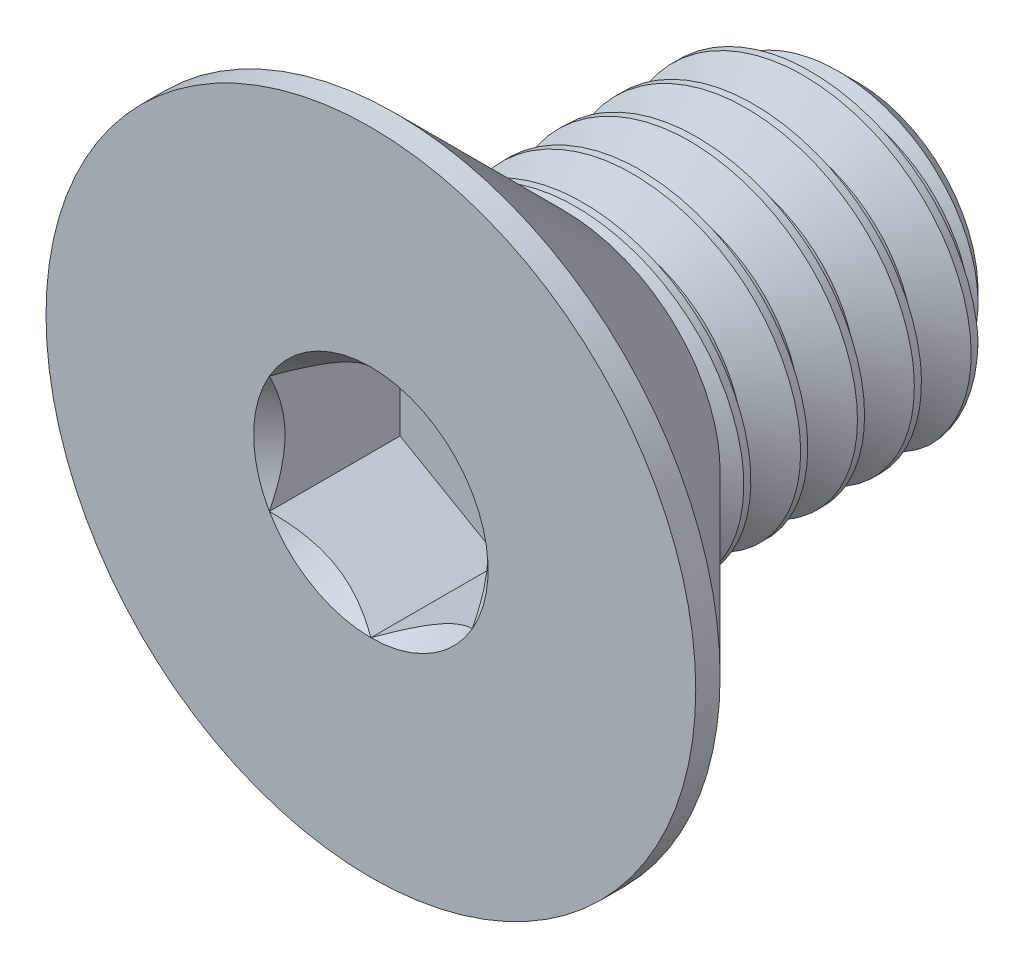
SolidWorks part; units mm, degrees
material "Stainless Steel (ferritic)"
ref_plane "Front" through (0, 0, 0) normal (0, 0, 1) x (1, 0, 0)
ref_plane "Top" through (0, 0, 0) normal (0, 1, 0) x (1, 0, 0)
ref_plane "Right" through (0, 0, 0) normal (1, 0, 0) x (0, 0, -1)
sketch "Sketch1" plane through (0, 0, 0) normal (1, 0, 0) x (0, 0, -1)
  line L0 (0, 4) -> (0.3, 4) construction
  line L1 (0.3, 4) -> (2.3, 2) construction
  line L2 (0, 2) -> (6, 2)
  line L3 (6, 2) -> (6, 0)
  line L4 (6, 0) -> (0, 0)
  line L5 (0, 0) -> (0, 4) construction
  line L6 (0, 4) -> (0, -4) construction
  line L7 (6, 2) -> (6, -2) construction
  line L8 (0, -4) -> (0.3, -4) construction
  line L9 (0.3, -4) -> (2.3, -2) construction
  line L11 (0, 2) -> (0, 0)
  line L12 (2.3, 2) -> (2.3, 0) construction
revolve "Revolve1" add sketch "Sketch1" angle 360 mid plane about L4
sketch "Sketch3" plane through (0, 0, -6) normal (0, 0, -1) x (-1, 0, 0)
  circle A0 centre (0, 0) radius 2
curve "Helix/Spiral1" pitch 0.7 height 6 radius 2 centre (0, 0, -6) axis (0, 0, 1) start towards (0, 1, 0)
sketch "Sketch2" plane through (0, 0, 0) normal (1, 0, 0) x (0, 0, -1)
  line L0 (6, 2) -> (6.6125, 2)
  line L1 (6.6125, 2) -> (6.35, 1.5453)
  line L2 (6.35, 1.5453) -> (6.2625, 1.5453)
  line L3 (6.2625, 1.5453) -> (6, 2)
  line L4 (6.1312, 1.7727) -> (6.4813, 1.7727) construction
  dimension "D1" = 60
  dimension "D2" = 0.0875
  dimension "D3" = 0.35
chamfer "Chamfer1" distance 0.525 angle 45 1 edges at (0, 2, -6)
sweep "Cut-Sweep1" cut profiles "Sketch2" path "Helix/Spiral1" align with end faces yes
sketch "Sketch7" plane through (0, 0, 0) normal (1, 0, 0) x (0, 0, -1)
  line L0 (0, 4) -> (0.3, 4) construction
  line L1 (0.3, 4) -> (2.3, 2) construction
  line L2 (0, 4) -> (0.3, 4)
  line L3 (0.3, 4) -> (2.3, 2)
  line L4 (2.3, 2) -> (2.3, 0) construction
  line L5 (2.3, 2) -> (2.3, 0)
  line L7 (0, 0) -> (0, 4) construction
  line L8 (0, 0) -> (0, 4)
  line L9 (0, 0) -> (2.3, 0)
  line L10 (4.4, 0) -> (-4.4, 0) construction
revolve "Revolve2" add sketch "Sketch7" angle 360 mid plane about L9
ref_plane "Plane1" through (0, 0, -2.3) normal (0, 0, 1) x (1, 0, 0)
sketch "Sketch8" plane through (0, 0, -2.3) normal (0, 0, 1) x (1, 0, 0)
  circle A0 centre (0, 0) radius 2
extrude "Boss-Extrude1" add sketch "Sketch8" against normal through all draft 45
sketch "Sketch5" plane through (0, 0, 0) normal (0, 0, 1) x (1, 0, 0)
  line L1 (1.25, -0.7217) -> (1.25, 0.7217)
  line L2 (1.25, 0.7217) -> (0, 1.4434)
  line L3 (0, 1.4434) -> (-1.25, 0.7217)
  line L4 (-1.25, 0.7217) -> (-1.25, -0.7217)
  line L5 (-1.25, -0.7217) -> (0, -1.4434)
  line L6 (0, -1.4434) -> (1.25, -0.7217)
  circle A0 centre (0, 0) radius 1.25 construction
  dimension "Hex" = 2.5
extrude "Cut-Extrude2" cut sketch "Sketch5" against normal blind 1.61
sketch "Sketch6" plane through (0, 0, 0) normal (0, 0, 1) x (1, 0, 0)
  circle A0 centre (0, 0) radius 1.4434
extrude "Cut-Extrude3" cut sketch "Sketch6" against normal blind 1.61 draft 45
sketch "Sketch9" [suppressed] plane through (0, 0, -5.5) normal (0, 0, 1) x (1, 0, 0)
  circle A1 centre (0, 0) radius 5
  circle A2 centre (0, 0) radius 5
  point P0 (0, 5)
  dimension "D1" = 0
extrude "Boss-Extrude2" [suppressed] add sketch "Sketch9" against normal offset from surface (18.5 mm away) 26 up to face at (0, 1.475, -6)
fillet "Fillet1" [suppressed] radius 0.4
sketch "Sketch10" plane through (0, 0, 0) normal (1, 0, 0) x (0, 0, -1)
  line L0 (6, 2) -> (6, -2) construction
  point P0 (4.95, -2)
  dimension "D1" = 1.05
equation "\"D3@Helix/Spiral1\" = \"Lg@Sketch1\""
equation "\"D2@Sketch2\" = \"D4@Helix/Spiral1\" * .125"
equation "\"D3@Sketch2\" = \"D4@Helix/Spiral1\" * .5"
equation "\"D1@Chamfer1\" = \"D4@Helix/Spiral1\" * .75"
equation "\"D1@Cut-Extrude2\" = \"Head Ht@Sketch1\" * .7"
equation "\"D1@Sketch10\" = \"D4@Helix/Spiral1\" * 1.5"
equation "\"D1@Cut-Extrude3\" = \"D1@Cut-Extrude2\""
equation "\"D1@Fillet1\" = \"Dia@Sketch1\" * .1"
